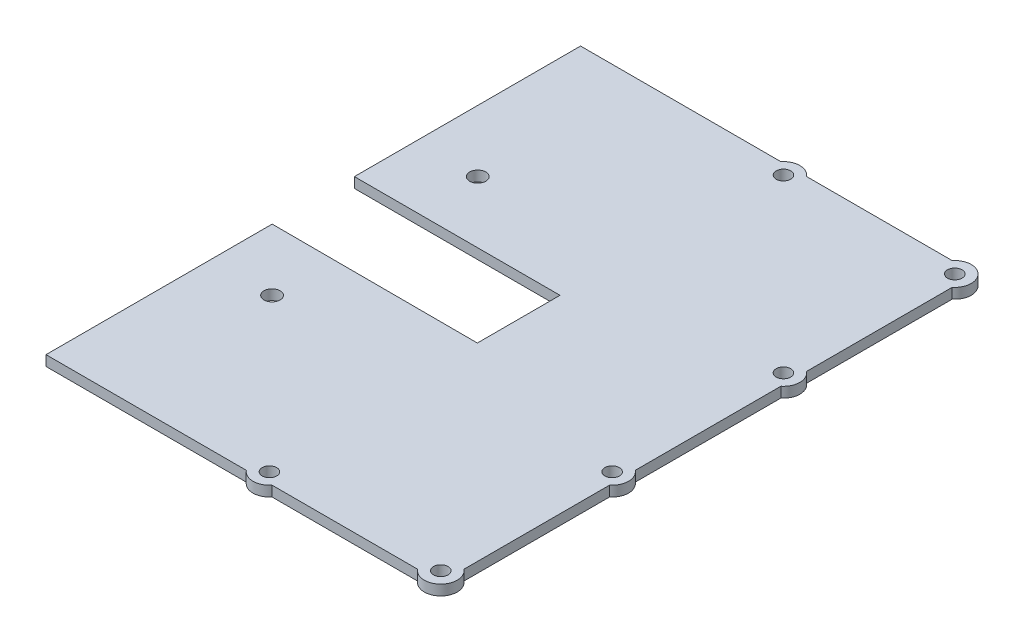
SolidWorks part; units mm, degrees
material "UHMW"
ref_plane "Front Plane" through (0, 0, 0) normal (0, 0, 1) x (1, 0, 0)
ref_plane "Top Plane" through (0, 0, 0) normal (0, 1, 0) x (1, 0, 0)
ref_plane "Right Plane" through (0, 0, 0) normal (1, 0, 0) x (0, 0, -1)
sketch "Sketch1" plane through (0, 0, 0) normal (0, 1, 0) x (1, 0, 0)
  circle A0 centre (65.8401, 3.175) radius 2.2479
  circle A1 centre (118.7568, 3.175) radius 2.2479
  circle A2 centre (118.7568, 56.0917) radius 2.2479
  circle A3 centre (118.7568, 109.0083) radius 2.2479
  circle A4 centre (118.7568, 161.925) radius 2.2479
  circle A5 centre (65.8401, 161.925) radius 2.2479
  line B0 (0, 165.1) -> (61.8745, 165.1)
  line B1 (0, 95.25) -> (0, 165.1)
  line B2 (0, 69.85) -> (0, 0)
  line B3 (61.8745, 0) -> (0, 0)
  line B4 (114.7912, 0) -> (69.8057, 0)
  line B5 (121.9318, 52.1261) -> (121.9318, 7.1406)
  line B6 (121.9318, 105.0428) -> (121.9318, 60.0572)
  line B7 (121.9318, 157.9594) -> (121.9318, 112.9739)
  line B8 (69.8057, 165.1) -> (114.7912, 165.1)
  line B9 (0, 95.25) -> (63.5, 95.25)
  line B10 (63.5, 95.25) -> (63.5, 69.7245)
  line B11 (63.5, 69.7245) -> (0, 69.85)
  arc B12 (69.8057, 165.1) -> (61.8745, 165.1) centre (65.8401, 161.925) ccw
  arc B13 (61.8745, 0) -> (69.8057, 0) centre (65.8401, 3.175) ccw
  arc B14 (114.7912, 0) -> (121.9318, 7.1406) centre (118.7568, 3.175) ccw
  arc B15 (121.9318, 52.1261) -> (121.9318, 60.0572) centre (118.7568, 56.0917) ccw
  arc B16 (121.9318, 105.0428) -> (121.9318, 112.9739) centre (118.7568, 109.0083) ccw
  arc B17 (121.9318, 157.9594) -> (114.7912, 165.1) centre (118.7568, 161.925) ccw
  dimension "D1" = 4.4958
sketch_block_instance "Block-bottomplate-1"
sketch_block "Block-bottomplate" parameters "D1"=63.5
extrude "Boss-Extrude1" add sketch "Sketch1" along normal blind 3.175
sketch "Sketch2" plane through (0, 0, 0) normal (0, -1, 0) x (1, 0, 0)
  line L0 (63.5, -69.7245) -> (0, -69.85) construction
  line L1 (0, -95.25) -> (63.5, -95.25) construction
  line L2 (0, -165.1) -> (0, -95.25) construction
  circle A0 centre (19.05, -50.7623) radius 2.4892
  circle A1 centre (19.05, -114.3) radius 2.4892
  point P4 (0, 0)
  dimension "D3" = 4.9784
  dimension "D1" = 19.05
  dimension "D2" = 19.05
  dimension "D4" = 19.05
extrude "Cut-Extrude1" cut sketch "Sketch2" against normal through all
equation "\"Unit Measure\"= \"BoundingVolume\" / \"Thickness\"'in^2"
